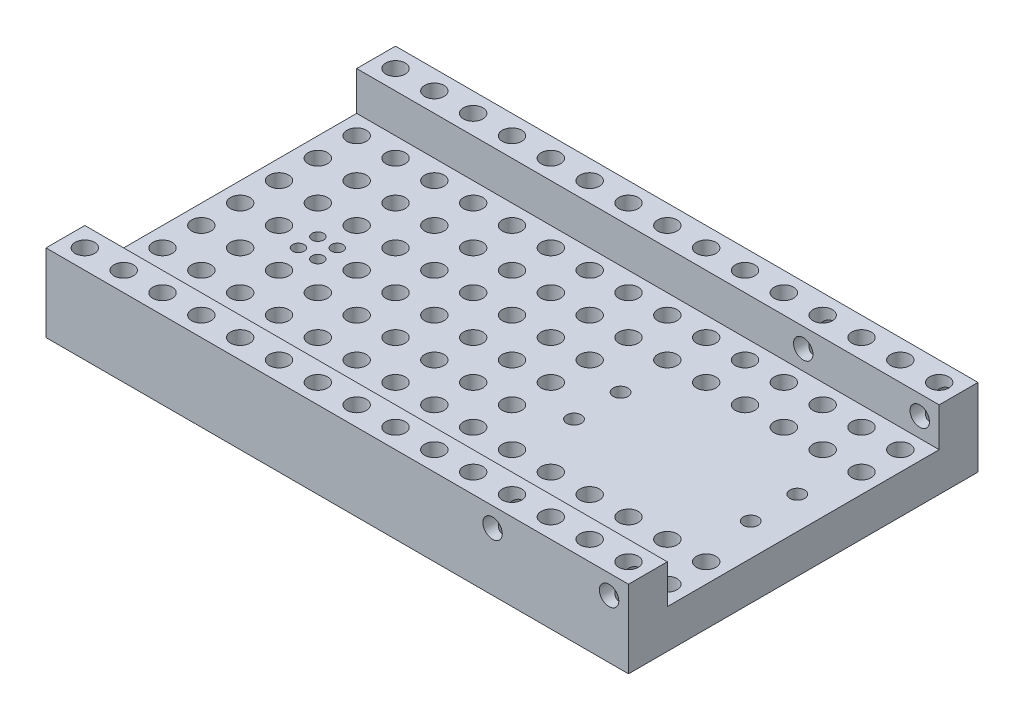
SolidWorks part; units mm, degrees
note: The reader was unsure of these and kept them because the rebuilt part matched: shared geometry of "Sketch1<3>", "Sketch1<4>".
ref_plane "Front Plane" through (0, 0, 0) normal (0, 0, 1) x (1, 0, 0)
ref_plane "Top Plane" through (0, 0, 0) normal (0, 1, 0) x (1, 0, 0)
ref_plane "Right Plane" through (0, 0, 0) normal (1, 0, 0) x (0, 0, -1)
sketch "Sketch1" plane through (0, 0, 0) normal (0, 1, 0) x (1, 0, 0)
  line L0 (-90.1724, 58.4763) -> (59.8276, 58.4763)
  line L1 (-90.1724, 68.4763) -> (59.8276, 68.4763)
  line L2 (-90.1724, 68.4763) -> (-90.1724, -21.5237)
  line L3 (-90.1724, -21.5237) -> (59.8276, -21.5237)
  line L4 (59.8276, 68.4763) -> (59.8276, -21.5237)
  line L5 (-90.1724, -11.5237) -> (59.8276, -11.5237)
  line L7 (2.9946, 13.4763) -> (53.9946, 13.4763)
  line L8 (2.9946, 13.4763) -> (2.9946, 34.4763)
  line L9 (2.9946, 34.4763) -> (53.9946, 34.4763)
  line L10 (53.9946, 13.4763) -> (53.9946, 34.4763)
  circle A0 centre (-67.6724, 25.9763) radius 1.5
  circle A1 centre (-62.6724, 25.9763) radius 1.5
  circle A2 centre (-62.6724, 20.9763) radius 1.5
  circle A3 centre (-67.6724, 20.9763) radius 1.5
  circle A4 centre (51.4946, 18.2763) radius 1.9
  circle A5 centre (5.9946, 18.2763) radius 1.9
  circle A6 centre (5.9946, 30.2763) radius 1.9
  circle A7 centre (51.4946, 30.2763) radius 1.9
  circle A8 centre (-85.1724, -16.5237) radius 2.5
  circle A9 centre (-75.1724, -16.5237) radius 2.5
  circle A10 centre (-65.1724, -16.5237) radius 2.5
  circle A11 centre (-55.1724, -16.5237) radius 2.5
  circle A12 centre (-45.1724, -16.5237) radius 2.5
  circle A13 centre (-35.1724, -16.5237) radius 2.5
  circle A14 centre (-25.1724, -16.5237) radius 2.5
  circle A15 centre (-15.1724, -16.5237) radius 2.5
  circle A16 centre (-5.1724, -16.5237) radius 2.5
  circle A17 centre (4.8276, -16.5237) radius 2.5
  circle A18 centre (14.8276, -16.5237) radius 2.5
  circle A19 centre (24.8276, -16.5237) radius 2.5
  circle A20 centre (34.8276, -16.5237) radius 2.5
  circle A21 centre (44.8276, -16.5237) radius 2.5
  circle A22 centre (54.8276, -16.5237) radius 2.5
  circle A23 centre (-75.1724, -6.5237) radius 2.5
  circle A24 centre (-65.1724, -6.5237) radius 2.5
  circle A25 centre (-55.1724, -6.5237) radius 2.5
  circle A26 centre (-45.1724, -6.5237) radius 2.5
  circle A27 centre (-35.1724, -6.5237) radius 2.5
  circle A28 centre (-25.1724, -6.5237) radius 2.5
  circle A29 centre (-15.1724, -6.5237) radius 2.5
  circle A30 centre (-5.1724, -6.5237) radius 2.5
  circle A31 centre (4.8276, -6.5237) radius 2.5
  circle A32 centre (14.8276, -6.5237) radius 2.5
  circle A33 centre (24.8276, -6.5237) radius 2.5
  circle A34 centre (34.8276, -6.5237) radius 2.5
  circle A35 centre (44.8276, -6.5237) radius 2.5
  circle A36 centre (54.8276, -6.5237) radius 2.5
  circle A37 centre (-75.1724, 3.4763) radius 2.5
  circle A38 centre (-65.1724, 3.4763) radius 2.5
  circle A39 centre (-55.1724, 3.4763) radius 2.5
  circle A40 centre (-45.1724, 3.4763) radius 2.5
  circle A41 centre (-35.1724, 3.4763) radius 2.5
  circle A42 centre (-25.1724, 3.4763) radius 2.5
  circle A43 centre (-15.1724, 3.4763) radius 2.5
  circle A44 centre (-5.1724, 3.4763) radius 2.5
  circle A45 centre (4.8276, 3.4763) radius 2.5
  circle A46 centre (14.8276, 3.4763) radius 2.5
  circle A47 centre (24.8276, 3.4763) radius 2.5
  circle A48 centre (34.8276, 3.4763) radius 2.5
  circle A49 centre (44.8276, 3.4763) radius 2.5
  circle A50 centre (54.8276, 3.4763) radius 2.5
  circle A51 centre (-75.1724, 13.4763) radius 2.5
  circle A52 centre (-65.1724, 13.4763) radius 2.5
  circle A53 centre (-55.1724, 13.4763) radius 2.5
  circle A54 centre (-45.1724, 13.4763) radius 2.5
  circle A55 centre (-35.1724, 13.4763) radius 2.5
  circle A56 centre (-25.1724, 13.4763) radius 2.5
  circle A57 centre (-15.1724, 13.4763) radius 2.5
  circle A58 centre (-5.1724, 13.4763) radius 2.5
  circle A65 centre (-75.1724, 23.4763) radius 2.5
  circle A67 centre (-55.1724, 23.4763) radius 2.5
  circle A68 centre (-45.1724, 23.4763) radius 2.5
  circle A69 centre (-35.1724, 23.4763) radius 2.5
  circle A70 centre (-25.1724, 23.4763) radius 2.5
  circle A71 centre (-15.1724, 23.4763) radius 2.5
  circle A72 centre (-5.1724, 23.4763) radius 2.5
  circle A79 centre (-75.1724, 33.4763) radius 2.5
  circle A81 centre (-55.1724, 33.4763) radius 2.5
  circle A82 centre (-45.1724, 33.4763) radius 2.5
  circle A83 centre (-35.1724, 33.4763) radius 2.5
  circle A84 centre (-25.1724, 33.4763) radius 2.5
  circle A85 centre (-15.1724, 33.4763) radius 2.5
  circle A86 centre (-5.1724, 33.4763) radius 2.5
  circle A93 centre (-75.1724, 43.4763) radius 2.5
  circle A94 centre (-65.1724, 43.4763) radius 2.5
  circle A95 centre (-55.1724, 43.4763) radius 2.5
  circle A96 centre (-45.1724, 43.4763) radius 2.5
  circle A97 centre (-35.1724, 43.4763) radius 2.5
  circle A98 centre (-25.1724, 43.4763) radius 2.5
  circle A99 centre (-15.1724, 43.4763) radius 2.5
  circle A100 centre (-5.1724, 43.4763) radius 2.5
  circle A107 centre (-75.1724, 53.4763) radius 2.5
  circle A108 centre (-65.1724, 53.4763) radius 2.5
  circle A109 centre (-55.1724, 53.4763) radius 2.5
  circle A110 centre (-45.1724, 53.4763) radius 2.5
  circle A111 centre (-35.1724, 53.4763) radius 2.5
  circle A112 centre (-25.1724, 53.4763) radius 2.5
  circle A113 centre (-15.1724, 53.4763) radius 2.5
  circle A114 centre (-5.1724, 53.4763) radius 2.5
  circle A115 centre (4.8276, 53.4763) radius 2.5
  circle A116 centre (14.8276, 53.4763) radius 2.5
  circle A117 centre (24.8276, 53.4763) radius 2.5
  circle A118 centre (34.8276, 53.4763) radius 2.5
  circle A119 centre (44.8276, 53.4763) radius 2.5
  circle A120 centre (54.8276, 53.4763) radius 2.5
  circle A121 centre (-75.1724, 63.4763) radius 2.5
  circle A122 centre (-65.1724, 63.4763) radius 2.5
  circle A123 centre (-55.1724, 63.4763) radius 2.5
  circle A124 centre (-45.1724, 63.4763) radius 2.5
  circle A125 centre (-35.1724, 63.4763) radius 2.5
  circle A126 centre (-25.1724, 63.4763) radius 2.5
  circle A127 centre (-15.1724, 63.4763) radius 2.5
  circle A128 centre (-5.1724, 63.4763) radius 2.5
  circle A129 centre (4.8276, 63.4763) radius 2.5
  circle A130 centre (14.8276, 63.4763) radius 2.5
  circle A131 centre (24.8276, 63.4763) radius 2.5
  circle A132 centre (34.8276, 63.4763) radius 2.5
  circle A133 centre (44.8276, 63.4763) radius 2.5
  circle A134 centre (54.8276, 63.4763) radius 2.5
  circle A149 centre (-85.1724, -6.5237) radius 2.5
  circle A150 centre (-85.1724, 3.4763) radius 2.5
  circle A151 centre (-85.1724, 13.4763) radius 2.5
  circle A152 centre (-85.1724, 23.4763) radius 2.5
  circle A153 centre (-85.1724, 33.4763) radius 2.5
  circle A154 centre (-85.1724, 43.4763) radius 2.5
  circle A155 centre (-85.1724, 53.4763) radius 2.5
  circle A156 centre (-85.1724, 63.4763) radius 2.5
  circle A158 centre (54.8276, 13.4763) radius 2.5 [skipped]
  circle A159 centre (54.8276, 23.4763) radius 2.5 [skipped]
  circle A160 centre (54.8276, 33.4763) radius 2.5 [skipped]
  circle A161 centre (44.8276, 33.4763) radius 2.5 [skipped]
  circle A162 centre (44.8276, 13.4763) radius 2.5 [skipped]
  circle A163 centre (44.8276, 23.4763) radius 2.5 [skipped]
  circle A164 centre (34.8276, 13.4763) radius 2.5 [skipped]
  circle A165 centre (34.8276, 23.4763) radius 2.5 [skipped]
  circle A166 centre (34.8276, 33.4763) radius 2.5 [skipped]
  circle A167 centre (24.8276, 33.4763) radius 2.5 [skipped]
  circle A168 centre (24.8276, 23.4763) radius 2.5 [skipped]
  circle A169 centre (24.8276, 13.4763) radius 2.5 [skipped]
  circle A170 centre (14.8276, 13.4763) radius 2.5 [skipped]
  circle A171 centre (14.8276, 33.4763) radius 2.5 [skipped]
  circle A172 centre (14.8276, 23.4763) radius 2.5 [skipped]
  circle A173 centre (4.8276, 33.4763) radius 2.5 [skipped]
  circle A174 centre (4.8276, 23.4763) radius 2.5 [skipped]
  circle A175 centre (4.8276, 13.4763) radius 2.5 [skipped]
  circle A176 centre (4.8276, 43.4763) radius 2.5 [skipped]
  circle A177 centre (14.8276, 43.4763) radius 2.5 [skipped]
  circle A178 centre (24.8276, 43.4763) radius 2.5 [skipped]
  circle A179 centre (34.8276, 43.4763) radius 2.5 [skipped]
  circle A180 centre (44.8276, 43.4763) radius 2.5 [skipped]
  circle A181 centre (54.8276, 43.4763) radius 2.5 [skipped]
  circle A182 centre (-65.1724, 23.4763) radius 2.5 [skipped]
  circle A183 centre (-65.1724, 33.4763) radius 2.5 [skipped]
  circle A184 centre (-75.1724, 73.4763) radius 2.5 [skipped]
  circle A185 centre (-65.1724, 73.4763) radius 2.5 [skipped]
  circle A186 centre (-55.1724, 73.4763) radius 2.5 [skipped]
  circle A187 centre (-45.1724, 73.4763) radius 2.5 [skipped]
  circle A188 centre (-35.1724, 73.4763) radius 2.5 [skipped]
  circle A189 centre (-25.1724, 73.4763) radius 2.5 [skipped]
  circle A190 centre (-15.1724, 73.4763) radius 2.5 [skipped]
  circle A191 centre (-5.1724, 73.4763) radius 2.5 [skipped]
  circle A192 centre (4.8276, 73.4763) radius 2.5 [skipped]
  circle A193 centre (14.8276, 73.4763) radius 2.5 [skipped]
  circle A194 centre (34.8276, 73.4763) radius 2.5 [skipped]
  circle A195 centre (44.8276, 73.4763) radius 2.5 [skipped]
  circle A196 centre (54.8276, 73.4763) radius 2.5 [skipped]
  circle A197 centre (-85.1724, 73.4763) radius 2.5 [skipped]
  circle A198 centre (24.8276, 73.4763) radius 2.5 [skipped]
  circle A199 centre (4.8276, 43.4763) radius 2.5
  circle A200 centre (14.8276, 43.4763) radius 2.5
  circle A201 centre (24.8276, 43.4763) radius 2.5
  circle A202 centre (34.8276, 43.4763) radius 2.5
  circle A203 centre (44.8276, 43.4763) radius 2.5
  circle A204 centre (54.8276, 43.4763) radius 2.5
  circle A205 centre (-65.1724, 33.4763) radius 2.5
  dimension "D5" = 3
  dimension "D10" = 51
  dimension "D12" = 2.5
  dimension "D13" = 3.8
  dimension "D14" = 4.8
  dimension "D18" = 5
  dimension "D1" = 150
  dimension "D2" = 90
  dimension "D3" = 10
  dimension "D4" = 10
  dimension "D8" = 22.5
  dimension "D9" = 42.5
  dimension "D11" = 21
  dimension "D17" = 3
  dimension "D19" = 5
  dimension "D20" = 5
  dimension "D23" = 35
  dimension "D6" = 2
  dimension "D7" = 2
  dimension "D15" = 2
  dimension "D16" = 2
  dimension "D21" = 15
  dimension "D22" = 10
  dimension "D24" = 7
  dimension "D25" = 2
extrude "Boss-Extrude1" add sketch "Sketch1" along normal blind 20 contours L4 L1 L2 L0 | L5 L2 L3 L4
extrude "Boss-Extrude2" add sketch "Sketch1<3>" along normal blind 10 contours L2 L5 L4 L0
sketch "Sketch1<3>" plane through (0, 0, 0) normal (0, 1, 0) x (1, 0, 0) same geometry as "Sketch1"
sketch "Sketch3" plane through (0, 0, 11.5237) normal (0, 0, -1) x (-1, 0, 0)
  line L0 (90.1724, 20) -> (-59.8276, 20) construction
  line L1 (-59.8276, 20) -> (-59.8276, 10) construction
  circle A0 centre (-54.8276, 15) radius 2.5
  circle A1 centre (-24.8276, 15) radius 2.5
  dimension "D1" = 5
  dimension "D2" = 5
  dimension "D4" = 5
  dimension "D3" = 2
extrude "Cut-Extrude1" cut sketch "Sketch3" against normal through all both and the other way through all contours A1 | A0
extrude "Boss-Extrude3" add sketch "Sketch1<4>" along normal blind 10 contours L7 L10 L9 L8 A7 A6 A5 A4
sketch "Sketch1<4>" plane through (0, 0, 0) normal (0, 1, 0) x (1, 0, 0) same geometry as "Sketch1"
